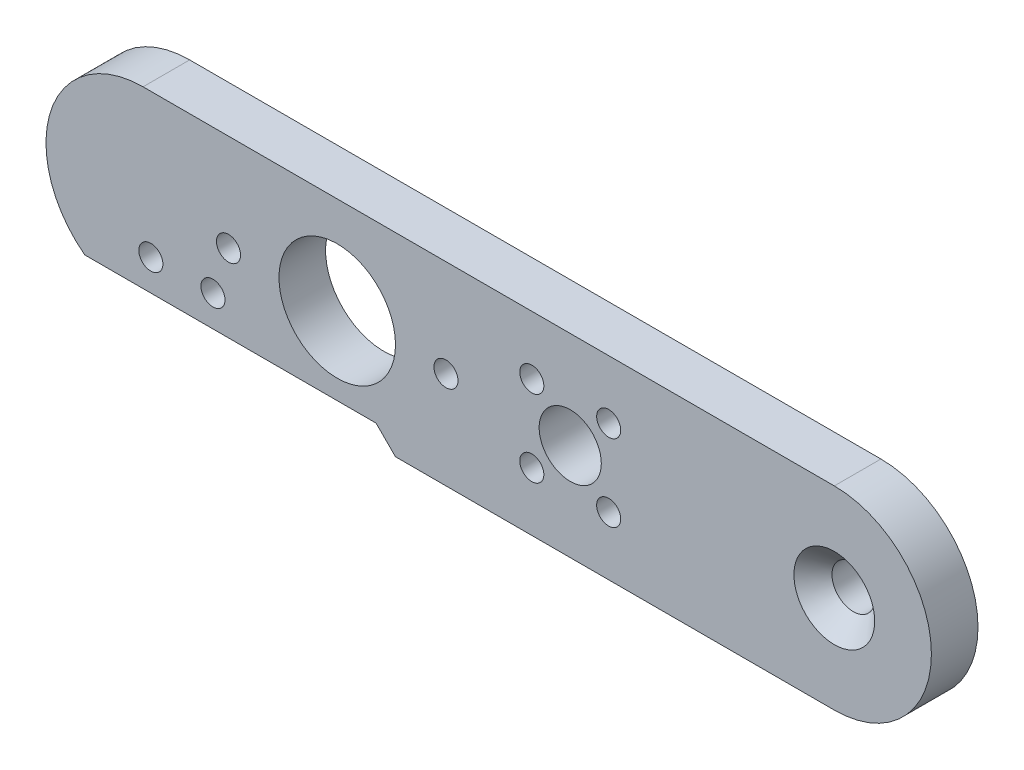
SolidWorks part; units mm, degrees
ref_plane "Front Plane" through (0, 0, 0) normal (0, 0, 1) x (1, 0, 0)
ref_plane "Top Plane" through (0, 0, 0) normal (0, 1, 0) x (1, 0, 0)
ref_plane "Right Plane" through (0, 0, 0) normal (1, 0, 0) x (0, 0, -1)
sketch "Sketch1" plane through (0, 0, 0) normal (0, 0, 1) x (1, 0, 0)
  line L0 (44.5, 0) -> (-44.5, 0) construction
  line L1 (44.5, -12.5) -> (-12, -12.5)
  line L2 (44.5, 12.5) -> (-44.5, 12.5)
  line L3 (10.5, 0) -> (10.5, 7) construction
  line L4 (10.5, 0) -> (17.5, 0) construction
  line L5 (10.5, 0) -> (15.4497, 4.9497) construction
  line L6 (3.5, 0) -> (17.5, 0) construction
  line L7 (10.5, 0) -> (5.5503, -4.9497) construction
  line L8 (10.5, 0) -> (15.4497, -4.9497) construction
  line L9 (-52, -10) -> (-14.5, -10)
  line L10 (-14.5, -10) -> (-12, -12.5)
  arc A0 (44.5, -12.5) -> (44.5, 12.5) centre (44.5, 0) ccw
  arc A1 (-44.5, 12.5) -> (-52, -10) centre (-44.5, 0) ccw
  circle A2 centre (10.5, 0) radius 4
  circle A3 centre (10.5, 0) radius 7 construction
  circle A4 centre (15.4497, 4.9497) radius 1.55
  circle A5 centre (5.5503, 4.9497) radius 1.55
  circle A6 centre (15.4497, -4.9497) radius 1.55
  circle A7 centre (5.5503, -4.9497) radius 1.55
  circle A8 centre (-19.5, 0) radius 7.5
  circle A9 centre (-5.5, 0) radius 1.55
  circle A10 centre (-33.5, 0) radius 1.55
  point P2 (0, 0)
  dimension "D2" = 12.5
  dimension "D3" = 8
  dimension "D5" = 14
  dimension "D7" = 3.1
  dimension "D10" = 3.1
  dimension "D13" = 3.1
  dimension "D14" = 3.1
  dimension "D17" = 15
  dimension "D1" = 89
  dimension "D4" = 34
  dimension "D6" = 45
  dimension "D8" = 45
  dimension "D9" = 45
  dimension "D11" = 59
  dimension "D12" = 22.5
  dimension "D15" = 14
  dimension "D16" = 14
  dimension "D18" = 30
extrude "Boss-Extrude1" add sketch "Sketch1" along normal blind 6
hole_wizard "CSK for M5 Flat Head Machine Screw1" positions "Sketch3" profile "Sketch4" countersink size "M5" standard "ANSI Metric" end condition through all
sketch "Sketch3" plane through (0, 0, 6) normal (0, 0, 1) x (1, 0, 0)
  point P0 (44.5, 0)
sketch "Sketch4" plane through (44.5, 0, 6) normal (1, 0, 0) x (0, -1, 0)
  line L0 (0, 0) -> (0, 6)
  line L1 (0, 6) -> (2.75, 6)
  line L2 (2.75, 6) -> (2.75, 2.45)
  line L3 (2.75, 2.45) -> (5.2, 0)
  line L5 (5.2, 0) -> (0, 0)
  line L6 (-2.75, 2.45) -> (-5.2, 0) construction
  line L11 (0, -6.35) -> (0, 107.95) construction
  dimension "Thru Hole Dia." = 5.5
  dimension "Thru Hole Depth" = 6
  dimension "Near C'Sink Dia." = 10.4
  dimension "Near C'Sink Angle" = 90
sketch "Sketch5" plane through (0, 0, 6) normal (0, 0, 1) x (1, 0, 0)
  line L0 (-49.9994, -6) -> (-25.0807, -6) construction
  line L1 (44.5, 12.5) -> (-44.5, 12.5) construction
  circle A0 centre (-35.5, -6) radius 1.55
  circle A1 centre (-43.5, -6) radius 1.55
  dimension "D2" = 3.1
  dimension "D3" = 3.1
  dimension "D1" = 18.5
  dimension "D4" = 16
  dimension "D5" = 8
extrude "Cut-Extrude1" cut sketch "Sketch5" against normal blind 3
sketch "Sketch6" plane through (0, 0, 3) normal (0, 0, 1) x (1, 0, 0)
  circle A0 centre (-43.5, -6) radius 3
  circle A1 centre (-35.5, -6) radius 3
  dimension "D1" = 6
extrude "Cut-Extrude2" cut sketch "Sketch6" against normal through all
